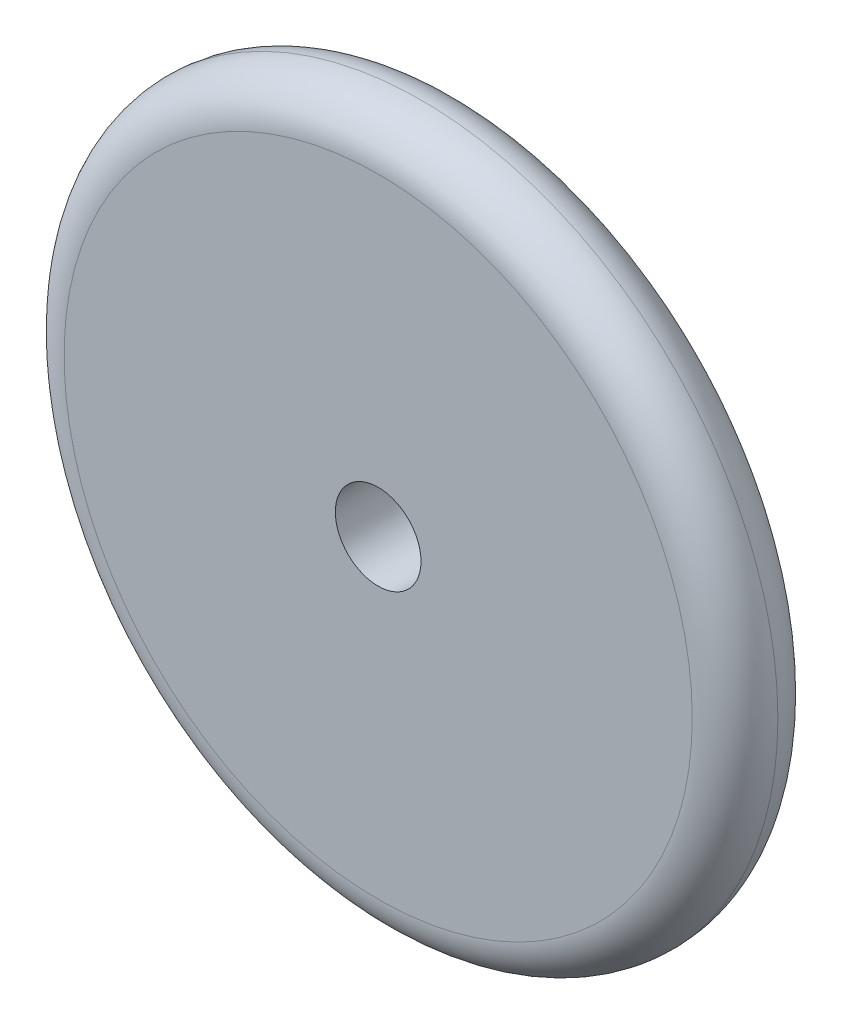
SolidWorks part; units mm, degrees
ref_plane "Front Plane" through (0, 0, 0) normal (0, 0, 1) x (1, 0, 0)
ref_plane "Top Plane" through (0, 0, 0) normal (0, 1, 0) x (1, 0, 0)
ref_plane "Right Plane" through (0, 0, 0) normal (1, 0, 0) x (0, 0, -1)
sketch "Sketch1" plane through (0, 0, 0) normal (0, 0, 1) x (1, 0, 0)
  circle A0 centre (0, 0) radius 125
  dimension "D1" = 250
extrude "Boss-Extrude1" add sketch "Sketch1" along normal blind 30
fillet "Fillet1" radius 15 2 edges at (125, 0, 0) (125, 0, 30)
sketch "Sketch2" plane through (0, 0, 30) normal (0, 0, 1) x (1, 0, 0)
  circle A0 centre (0, 0) radius 15
  dimension "D1" = 30
extrude "Cut-Extrude1" cut sketch "Sketch2" against normal blind 30
